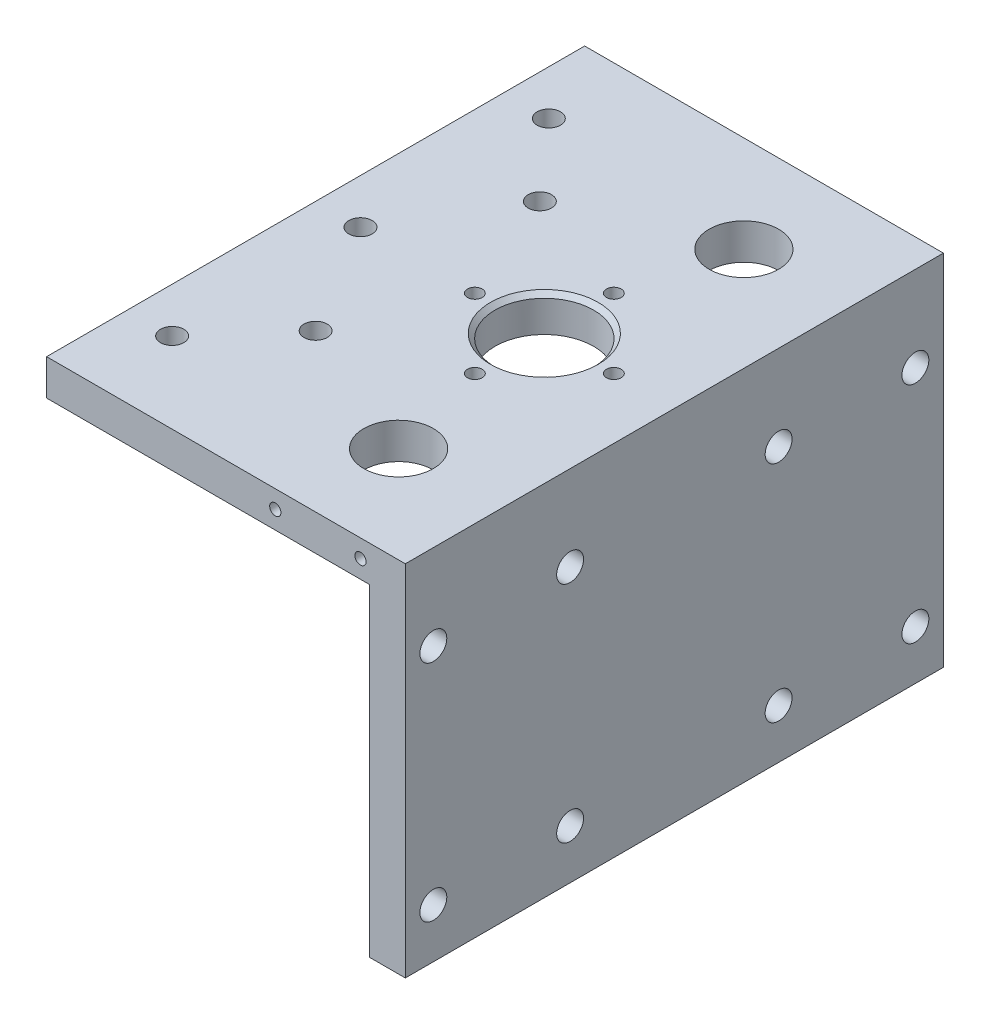
SolidWorks part; units mm, degrees
material "Lega 1060"
ref_plane "Piano frontale" through (0, 0, 0) normal (0, 0, 1) x (1, 0, 0)
ref_plane "Piano superiore" through (0, 0, 0) normal (0, 1, 0) x (1, 0, 0)
ref_plane "Piano destro" through (0, 0, 0) normal (1, 0, 0) x (0, 0, -1)
sketch "Schizzo1" plane through (0, 0, 0) normal (0, 0, 1) x (1, 0, 0)
  line L0 (0, 0) -> (-80, 0)
  line L1 (-80, 0) -> (-80, -8)
  line L2 (-80, -8) -> (-8, -8)
  line L3 (-8, -8) -> (-8, -80)
  line L4 (-8, -80) -> (0, -80)
  line L5 (0, -80) -> (0, 0)
  dimension "D1" = 80
  dimension "D2" = 80
  dimension "D3" = 8
  dimension "D4" = 8
extrude "Estrusione-Estrusione1" add sketch "Schizzo1" along normal blind 120
sketch "Schizzo12" plane through (0, 0, 0) normal (1, 0, 0) x (0, 0, -1)
  line L0 (0, -8) -> (-120, -8) construction
  line L1 (-21.5, 0) -> (-21.5, 40.839) construction
  line L5 (0, -80) -> (0, 0) construction
  line L6 (-120, -80) -> (-120, 0) construction
  line L7 (-120, 0) -> (0, 0) construction
  line L8 (-113.75, -19) -> (9.6992, -19) construction
  line L9 (-113.75, -69) -> (15.4001, -69) construction
  line L10 (-98.5, -47.4454) -> (-98.5, 40.839) construction
  circle A0 centre (-113.75, -19) radius 3
  circle A1 centre (-83.25, -19) radius 3
  circle A6 centre (-36.75, -19) radius 3
  circle A7 centre (-6.25, -19) radius 3
  circle A10 centre (-83.25, -69) radius 3
  circle A11 centre (-113.75, -69) radius 3
  circle A12 centre (-6.25, -69) radius 3
  circle A13 centre (-36.75, -69) radius 3
  dimension "D1" = 6
  dimension "D5" = 30.5
  dimension "D6" = 30.5
  dimension "D7" = 30.5
  dimension "D8" = 30.5
  dimension "D2" = 8
  dimension "D3" = 11
  dimension "D4" = 61
  dimension "D9" = 21.5
  dimension "D10" = 21.5
sketch "Schizzo6" plane through (0, 0, 0) normal (0, 1, 0) x (1, 0, 0)
  line L0 (-23, -0.5808) -> (-23, -110.5835) construction
  line L2 (0, 0) -> (-80, 0) construction
  line L3 (-32.5218, -60) -> (-8.0464, -60) construction
  line L6 (0, -120) -> (-80, -120) construction
  circle A0 centre (-23, -21.5) radius 7.75
  circle A1 centre (-23, -98.5) radius 7.75
  dimension "D2" = 15.5
  dimension "D1" = 15
  dimension "D3" = 21.5
  dimension "D4" = 38.5
extrude "Taglio-Estrusione2" cut sketch "Schizzo6" against normal up to next
sketch "Schizzo7" plane through (0, 0, 0) normal (0, 1, 0) x (1, 0, 0)
  line L0 (-83.5082, -60) -> (3.6289, -60) construction
  line L1 (0, -120) -> (-80, -120) construction
  line L2 (0, 0) -> (-80, 0) construction
  line L3 (-23, -21.5) -> (-23, -98.5) construction
  line L4 (0, -120) -> (0, 0) construction
  circle A0 centre (-29, -60) radius 11
  dimension "D1" = 22
  dimension "D3" = 29
extrude "Taglio-Estrusione3" cut sketch "Schizzo7" against normal up to next
hole_wizard "M4 Tapped Hole1" positions "Schizzo9" profile "Schizzo8" tap size "M4" standard "ISO" end condition through all
sketch "Schizzo9" plane through (0, 0, 0) normal (0, 1, 0) x (1, 0, 0)
  line L0 (-18.4657, -60) -> (-13.5, -60) construction
  line L2 (-29, -57.7684) -> (-29, -66.5063) construction
  circle A2 centre (-29, -60) radius 11 construction
  point P0 (-29, -44.5)
  point P2 (-44.5, -60)
  point P4 (-29, -75.5)
  point P8 (-13.5, -60)
  point P20 (-29, -60)
  dimension "D1" = 31
  dimension "D2" = 15.5
  dimension "D3" = 15.5
sketch "Schizzo8" plane through (-29, 0, 44.5) normal (1, 0, 0) x (0, 0, 1)
  line L0 (0, 0) -> (0, 80)
  line L1 (0, 80) -> (1.65, 80)
  line L2 (1.65, 80) -> (1.65, 0)
  line L5 (1.65, 0) -> (0, 0)
  line L11 (0, -6.35) -> (0, 107.95) construction
  dimension "Thread Major Dia." = 3.3
  dimension "Thru Tap Drill Depth" = 80
extrude "Taglio-Estrusione4" cut sketch "Schizzo12" against normal blind 10
sketch "Schizzo14" plane through (0, 0, 0) normal (0, 1, 0) x (1, 0, 0)
  line L0 (-70, 0) -> (-70, -120) construction
  line L1 (0, 0) -> (-80, 0) construction
  line L2 (0, -120) -> (-80, -120) construction
  line L3 (-80, -120) -> (-80, 0) construction
  line L4 (-55, 0) -> (-55, -120) construction
  line L5 (-23, -98.5) -> (-80, -98.5) construction
  line L6 (-80, -60) -> (0, -60) construction
  line L7 (0, -120) -> (0, 0) construction
  line L8 (-23, -21.5) -> (-80, -21.5) construction
  circle A0 centre (-70, -18) radius 2.6
  circle A1 centre (-70, -60) radius 2.6
  circle A2 centre (-70, -102) radius 2.6
  circle A3 centre (-55, -35) radius 2.6
  circle A4 centre (-55, -85) radius 2.6
  dimension "D3" = 5.2
  dimension "D4" = 5.2
  dimension "D5" = 5.2
  dimension "D6" = 5.2
  dimension "D7" = 5.2
  dimension "D1" = 10
  dimension "D2" = 25
  dimension "D8" = 35
  dimension "D9" = 35
  dimension "D10" = 25
  dimension "D11" = 42
  dimension "D12" = 15
extrude "Taglio-Estrusione5" cut sketch "Schizzo14" against normal blind 10
chamfer "Smusso2" distance 1 angle 45 1 edges at (-40, 0, 60)
sketch "Schizzo15" plane through (0, 0, 120) normal (0, 0, 1) x (1, 0, 0)
  line L0 (-80, -4) -> (0, -4) construction
  line L1 (-80, 0) -> (-80, -8) construction
  line L2 (0, -80) -> (0, 0) construction
  point P6 (-10, -4)
  point P7 (-29, -4)
  dimension "D1" = 10
  dimension "D2" = 19
hole_wizard "Foro filettato M3-1" positions "Schizzo17" profile "Schizzo16" tap size "M3" standard "ISO"
sketch "Schizzo17" plane through (0, 0, 120) normal (0, 0, 1) x (1, 0, 0)
  point P0 (-10, -4)
  point P3 (-29, -4)
sketch "Schizzo16" plane through (-10, -4, 120) normal (1, 0, 0) x (0, -1, 0)
  line L0 (0, 0) -> (0, 10.7511)
  line L1 (0, 10.7511) -> (1.25, 10)
  line L2 (1.25, 10) -> (1.25, 0)
  line L5 (1.25, 0) -> (0, 0)
  line L10 (0, 10.7511) -> (-1.25, 10) construction
  line L11 (0, -6.35) -> (0, 107.95) construction
  dimension "Tap Drill Dia." = 2.5
  dimension "Tap Drill Depth" = 10
  dimension "Drill Angle" = 118
cosmetic thread "Filettatura del foro1" parameters "D1"=8, "D2"=3
cosmetic thread "Filettatura del foro2" parameters "D1"=8, "D2"=3
